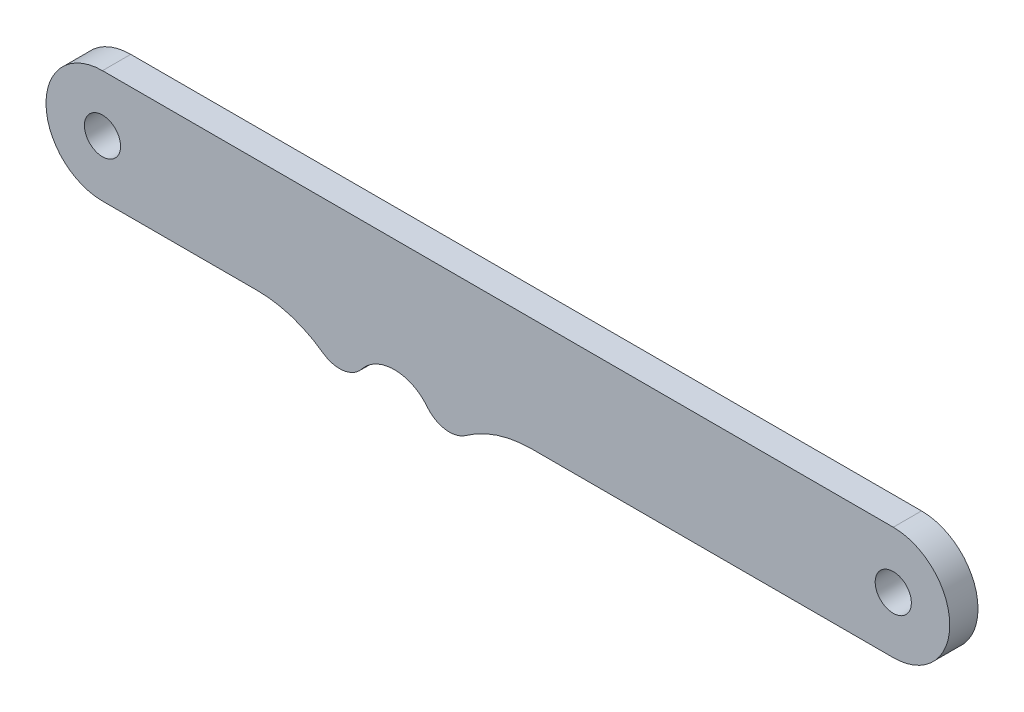
SolidWorks part; units mm, degrees
ref_plane "Front Plane" through (0, 0, 0) normal (0, 0, 1) x (1, 0, 0)
ref_plane "Top Plane" through (0, 0, 0) normal (0, 1, 0) x (1, 0, 0)
ref_plane "Right Plane" through (0, 0, 0) normal (1, 0, 0) x (0, 0, -1)
sketch "Sketch1" plane through (0, 0, 0) normal (0, 0, 1) x (1, 0, 0)
  line L2 (0, 0) -> (-88.9, 0) construction
  line L3 (0, -6.35) -> (-40.6215, -6.35)
  line L4 (0, 6.35) -> (-88.9, 6.35)
  line L5 (-71.522, -6.35) -> (-88.9, -6.35)
  arc A4 (0, -6.35) -> (0, 6.35) centre (0, 0) ccw
  arc A5 (-88.9, 6.35) -> (-88.9, -6.35) centre (-88.9, 0) ccw
  circle A6 centre (0, 0) radius 2.032
  circle A7 centre (-88.9, 0) radius 2.032
  arc A8 (-51.8991, -13.2099) -> (-60.2444, -13.2099) centre (-56.0718, -11.049) ccw
  arc A9 (-51.8991, -13.2099) -> (-40.6215, -6.35) centre (-40.6215, -19.05) cw
  arc A10 (-60.2444, -13.2099) -> (-71.522, -6.35) centre (-71.522, -19.05) ccw
  point P2 (-44.45, 0)
  dimension "D1" = 6.35
  dimension "D3" = 4.064
  dimension "D5" = 9.398
  dimension "D6" = 12.7
  dimension "D2" = 88.9
  dimension "D4" = 57.15
extrude "Boss-Extrude1" add sketch "Sketch1" along normal blind 3.175
fillet "Fillet1" radius 3.175 2 edges at (-60.2444, -13.2099, 1.5875) (-51.8991, -13.2099, 1.5875)
